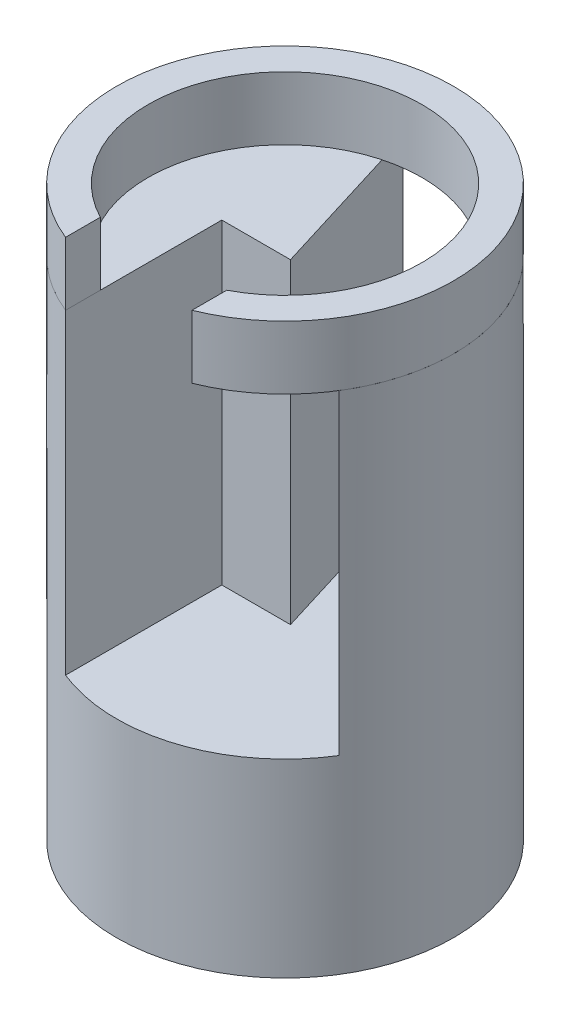
SolidWorks part; units mm, degrees
ref_plane "Front Plane" through (0, 0, 0) normal (0, 0, 1) x (1, 0, 0)
ref_plane "Top Plane" through (0, 0, 0) normal (0, 1, 0) x (1, 0, 0)
ref_plane "Right Plane" through (0, 0, 0) normal (1, 0, 0) x (0, 0, -1)
sketch "Sketch2" plane through (0, 0, 0) normal (0, 1, 0) x (1, 0, 0)
  circle A0 centre (0, 0) radius 101.6
  dimension "D1" = 203.2
extrude "Boss-Extrude1" add sketch "Sketch2" along normal blind 304.8
sketch "Sketch3" plane through (0, 304.8, 0) normal (0, 1, 0) x (1, 0, 0)
  circle A0 centre (0, 0) radius 82.55
  circle A1 centre (0, 0) radius 101.6 construction
  circle A2 centre (0, 0) radius 101.6
  dimension "D1" = 165.1
extrude "Boss-Extrude2" add sketch "Sketch3" along normal blind 38.1 separate body
sketch "Sketch4" plane through (0, 342.9, 0) normal (0, 1, 0) x (1, 0, 0)
  line L1 (-38.1, 0) -> (38.1, 0)
  line L2 (-38.1, 0) -> (-38.1, -101.6)
  line L3 (-38.1, -101.6) -> (38.1, -101.6)
  line L4 (38.1, 0) -> (38.1, -101.6)
  line L8 (-26.8987, 98.0249) -> (32.9028, -96.176)
  line L9 (-26.8987, 98.0249) -> (33.7891, 116.7129)
  line L10 (32.9028, -96.176) -> (93.5906, -77.488)
  line L11 (33.7891, 116.7129) -> (93.5906, -77.488)
  line L12 (3.4452, 107.3689) -> (63.2467, -86.832) construction
  line L13 (0, 0) -> (0, 101.6) construction
  circle A0 centre (0, 0) radius 101.6 construction
  point P4 (0, 0)
  circle M5 centre (0, 0) radius 101.6
  circle M6 centre (0, 0) radius 82.55
  dimension "D1" = 76.2
  dimension "D2" = 63.5
  dimension "D3" = 203.2
  dimension "D4" = 17.116
  dimension "D5" = 6.7193
extrude "Cut-Extrude1" cut sketch "Sketch4" against normal blind 228.6 contours L8 L1 L2 M6 | L8 L2 M6 M5 | L8 L4 M6 M5 | L1 L8 L4 M6 region at (-10.3974, 342.9, 43.1779) region at (25.5191, 342.9, 31.5319) region at (-4.199, 342.9, 89.8865) region at (33.9537, 342.9, 84.3011)
extrude "Cut-Extrude2" cut sketch "Sketch4<4>" against normal blind 190.5 from offset 38.1 contours L11 L4 M6 M5 | L11 L8 L1 L4 M6 | L11 L8 M5 M6 region at (32.4275, 342.9, -19.3523) region at (11.1293, 342.9, -88.9086) region at (62.6882, 342.9, 64.9023) offset against normal yes
sketch "Sketch4<4>" plane through (0, 342.9, 0) normal (0, 1, 0) x (1, 0, 0) same geometry as "Sketch4"
